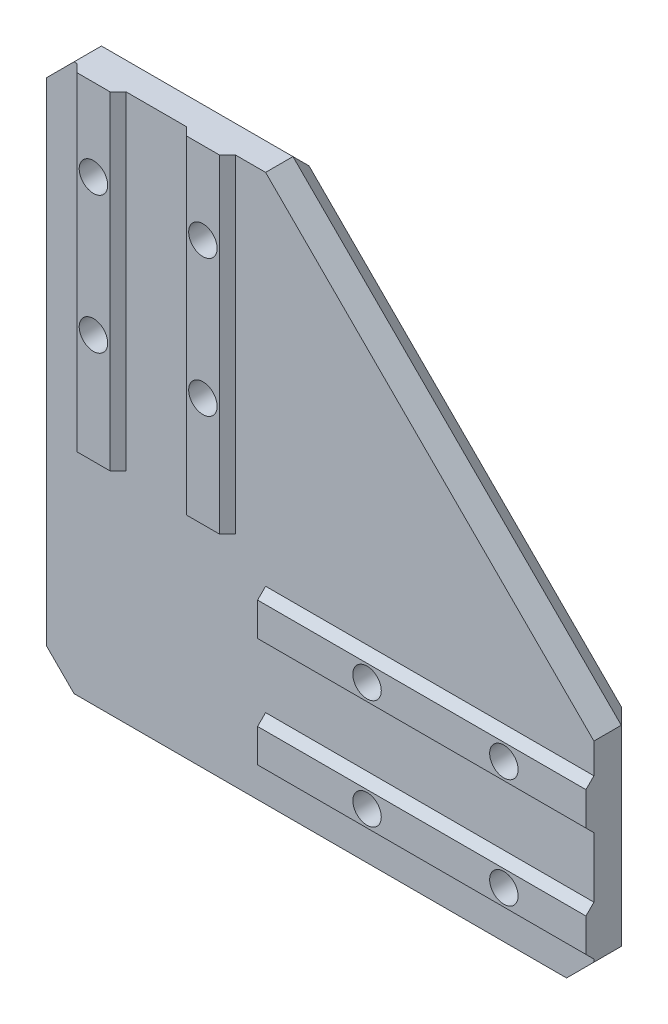
SolidWorks part; units mm, degrees
ref_plane "Płaszczyzna przednia" through (0, 0, 0) normal (0, 0, 1) x (1, 0, 0)
ref_plane "Płaszczyzna górna" through (0, 0, 0) normal (0, 1, 0) x (1, 0, 0)
ref_plane "Płaszczyzna prawa" through (0, 0, 0) normal (1, 0, 0) x (0, 0, -1)
sketch "Sketch1" plane through (0, 0, 0) normal (0, 0, 1) x (1, 0, 0)
  line L0 (0, 0) -> (100, 0)
  line L1 (100, 0) -> (100, 40)
  line L2 (100, 40) -> (40, 100)
  line L3 (40, 100) -> (0, 100)
  line L4 (0, 100) -> (0, 0)
  line L5 (10, 100) -> (10, 0) construction
  line L6 (30, 100) -> (30, 0) construction
  line L8 (100, 30) -> (0, 30) construction
  dimension "D1" = 40
  dimension "D2" = 40
  dimension "D3" = 100
extrude "Boss-Extrude1" add sketch "Sketch1" along normal blind 10
sketch "Sketch2" plane through (0, 0, 0) normal (0, 0, 1) x (1, 0, 0)
  line L5 (10, 100) -> (10, 0) construction
  line L6 (30, 100) -> (30, 0) construction
  line L7 (100, 10) -> (0, 10) construction
  line L8 (100, 30) -> (0, 30) construction
  line L9 (0, 0) -> (100, 0) construction
  line L10 (0, 100) -> (0, 0) construction
  line L11 (100, 0) -> (100, 40) construction
  line L12 (0, 100) -> (0, 0) construction
  line L13 (40, 100) -> (0, 100) construction
  line L14 (0, 0) -> (100, 0) construction
  circle A0 centre (10, 85) radius 2.6
  circle A1 centre (30, 85) radius 2.6
  circle A2 centre (10, 60) radius 2.6
  circle A3 centre (30, 60) radius 2.6
  circle A4 centre (85, 30) radius 2.6
  circle A5 centre (85, 10) radius 2.6
  circle A6 centre (60, 10) radius 2.6
  circle A7 centre (60, 30) radius 2.6
  dimension "D9" = 60
  dimension "D3" = 5.2
  dimension "D1" = 10
  dimension "D2" = 10
  dimension "D4" = 15
  dimension "D5" = 20
  dimension "D6" = 60
  dimension "D7" = 15
  dimension "D8" = 20
extrude "Cut-Extrude1" cut sketch "Sketch2" along normal through all
sketch "Sketch3" plane through (0, 0, 0) normal (0, 0, 1) x (1, 0, 0)
  line L0 (0, 100) -> (0, 0) construction
  line L1 (100, 0) -> (100, 40) construction
  line L2 (100, 25.5) -> (40, 25.5)
  line L3 (100, 25.5) -> (100, 34.5)
  line L4 (100, 34.5) -> (40, 34.5)
  line L5 (40, 25.5) -> (40, 34.5)
  line L6 (40, 100) -> (0, 100) construction
  line L7 (100, 5.5) -> (40, 5.5)
  line L8 (100, 5.5) -> (100, 14.5)
  line L9 (100, 14.5) -> (40, 14.5)
  line L10 (40, 5.5) -> (40, 14.5)
  line L11 (14.5, 100) -> (5.5, 100)
  line L12 (14.5, 100) -> (14.5, 40)
  line L13 (14.5, 40) -> (5.5, 40)
  line L14 (5.5, 100) -> (5.5, 40)
  line L15 (0, 0) -> (100, 0) construction
  line L16 (34.5, 100) -> (25.5, 100)
  line L17 (34.5, 100) -> (34.5, 40)
  line L18 (34.5, 40) -> (25.5, 40)
  line L19 (25.5, 100) -> (25.5, 40)
  circle A0 centre (60, 30) radius 2.6 construction
  circle A1 centre (60, 10) radius 2.6 construction
  circle A2 centre (30, 60) radius 2.6 construction
  circle A3 centre (10, 60) radius 2.6 construction
  dimension "D3" = 4.5
  dimension "D6" = 4.5
  dimension "D9" = 4.5
  dimension "D10" = 4.5
  dimension "D1" = 40
  dimension "D2" = 40
  dimension "D4" = 9
  dimension "D5" = 9
  dimension "D7" = 9
  dimension "D8" = 9
  dimension "D11" = 40
  dimension "D12" = 40
extrude "Boss-Extrude3" add sketch "Sketch3" along normal blind 1.46 from surface starting at face at (87.6, 30, 10)
extrude "Cut-Extrude2" cut sketch "Sketch2<2>" along normal through all both and the other way through all
sketch "Sketch2<2>" plane through (0, 0, 0) normal (0, 0, 1) x (1, 0, 0) same geometry as "Sketch2"
chamfer "Chamfer1" distance 1.46 angle 45 8 edges at (14.5, 70, 11.46) (5.5, 70, 11.46) (25.5, 70, 11.46) (34.5, 70, 11.46) (70, 5.5, 11.46) (70, 14.5, 11.46) (70, 25.5, 11.46) (70, 34.5, 11.46)
sketch "Sketch4" plane through (0, 0, 0) normal (0, 0, 1) x (1, 0, 0)
  circle A0 centre (10, 85) radius 4.5
  circle A1 centre (30, 85) radius 4.5
  circle A2 centre (30, 60) radius 4.5
  circle A3 centre (10, 60) radius 4.5
  circle A4 centre (60, 30) radius 4.5
  circle A5 centre (85, 30) radius 4.5
  circle A6 centre (85, 10) radius 4.5
  circle A7 centre (60, 10) radius 4.5
  dimension "D1" = 9
extrude "Cut-Extrude3" cut sketch "Sketch4" along normal blind 5 from surface starting at face at (87.6, 30, 0)
chamfer "Chamfer2" distance 5 angle 45 8 edges at (100, 0, 5) (0, 100, 5) (0, 0, 5) (50, 0, 0) (0, 50, 0) (20, 100, 0) (100, 20, 0) (70, 70, 0)
